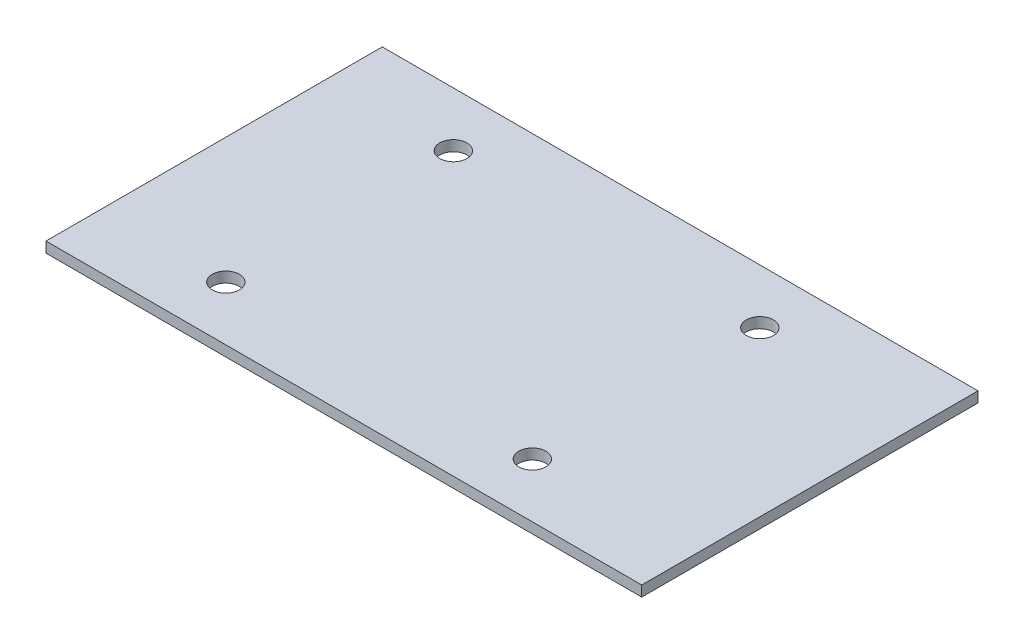
SolidWorks part; units mm, degrees
material "Cast Alloy Steel"
ref_plane "Front Plane" through (0, 0, 0) normal (0, 0, 1) x (1, 0, 0)
ref_plane "Top Plane" through (0, 0, 0) normal (0, 1, 0) x (1, 0, 0)
ref_plane "Right Plane" through (0, 0, 0) normal (1, 0, 0) x (0, 0, -1)
sketch "Sketch1" plane through (0, 0, 0) normal (0, 1, 0) x (1, 0, 0)
  line L1 (90, 50.8) -> (-90, 50.8)
  line L2 (90, 50.8) -> (90, -50.8)
  line L3 (90, -50.8) -> (-90, -50.8)
  line L4 (-90, 50.8) -> (-90, -50.8)
  line L5 (90, 50.8) -> (-90, -50.8) construction
  line L6 (90, -50.8) -> (-90, 50.8) construction
  circle A0 centre (-52.0875, 34.3735) radius 4.1
  circle A1 centre (40.5125, 34.3735) radius 4.1
  circle A2 centre (40.5125, -34.3735) radius 4.1
  circle A3 centre (-52.0875, -34.3735) radius 4.1
  point P0 (0, 0)
  dimension "D3" = 8.2
  dimension "D1" = 101.6
  dimension "D2" = 180
extrude "Boss-Extrude1" add sketch "Sketch1" along normal blind 3.175
